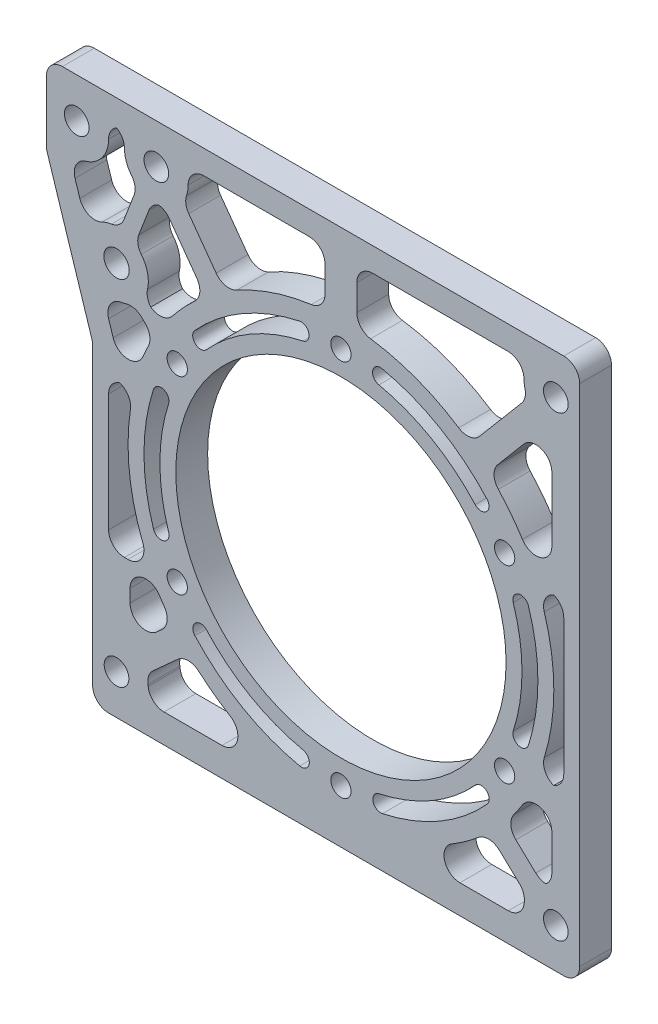
SolidWorks part; units mm, degrees
material "Thornel Mat VMA"
ref_plane "前视基准面" through (0, 0, 0) normal (0, 0, 1) x (1, 0, 0)
ref_plane "上视基准面" through (0, 0, 0) normal (0, 1, 0) x (1, 0, 0)
ref_plane "右视基准面" through (0, 0, 0) normal (1, 0, 0) x (0, 0, -1)
sketch "草图1" plane through (0, 0, 0) normal (0, 0, 1) x (1, 0, 0)
  line L0 (0, 27) -> (27, 27) construction
  line L1 (27, 27) -> (27, 0) construction
  line L2 (0, 27) -> (-37, 27) construction
  line L3 (-37, 27) -> (-31.2, 8.8931)
  line L4 (0, 0) -> (0, 50000) construction
  line L5 (-37, 27) -> (-37, 37)
  line L6 (-37, 37) -> (27, 37)
  line L7 (27, 37) -> (27, 27) construction
  line L8 (27, 37) -> (30, 37)
  line L9 (30, 37) -> (30, -30.45)
  line L10 (0, -27) -> (27, -27) construction
  line L11 (-31.2, -30.45) -> (-31.2, 8.8931)
  line L12 (-31.2, -30.45) -> (30, -30.45)
  circle A0 centre (0, 0) radius 18.5 construction
  circle A1 centre (0, 0) radius 20.75
  circle A2 centre (-28.2, 19) radius 1.6
  circle A3 centre (0, 0) radius 27
  circle A4 centre (0, 0) radius 23.75 construction
  circle A5 centre (0, 23.75) radius 1.275
  circle A6 centre (20.5681, 11.875) radius 1.275
  circle A7 centre (20.5681, -11.875) radius 1.275
  circle A8 centre (0, -23.75) radius 1.275
  circle A9 centre (-20.5681, -11.875) radius 1.275
  circle A10 centre (-20.5681, 11.875) radius 1.275
  circle A11 centre (-33.2, 32) radius 1.55
  circle A12 centre (-23.2, 32) radius 1.55
  circle A13 centre (27, 32) radius 1.55
  circle A14 centre (27, -25.45) radius 1.55
  circle A15 centre (-28.2, -25.45) radius 1.55
  point P12 (0, 0)
  point P30 (0, 0)
  dimension "D2" = 3
  dimension "D5" = 3.2
  dimension "D6" = 54
  dimension "D7" = 47.5
  dimension "D8" = 2.55
  dimension "D12" = 37
  dimension "D14" = 3.1
  dimension "D3" = 19
  dimension "D4" = 28.2
  dimension "D10" = 10
  dimension "D11" = 37
  dimension "D13" = 10
  dimension "D15" = 5
  dimension "D16" = 5
  dimension "D17" = 5
  dimension "D18" = 5
  dimension "D19" = 3
  dimension "D20" = 3
  dimension "D21" = 3
  dimension "D9" = 6
extrude "凸台-拉伸1" add sketch "草图1" along normal blind 4 contours A3 L2 L3 | A3 A1 A2 | A3 L1 L0 region at (-36.0493, 32, 0) region at (-26.2363, 0, 0)
sketch "草图3" plane through (0, 0, 4) normal (0, 0, 1) x (1, 0, 0)
  line L0 (-19.7359, 34) -> (23.5359, 34)
  line L1 (-19.7359, 34) -> (-37, 34)
  line L2 (-37, 27) -> (-37, 37) construction
  line L3 (-37, 37) -> (30, 37) construction
  line L4 (-34.2118, 28.1301) -> (-31.8273, 20.686)
  line L5 (-37, 27) -> (-31.2, 8.8931) construction
  line L6 (-22.1882, 28.1301) -> (-24.5727, 20.686)
  line L7 (-28.2, 19) -> (-28.2, 50019) construction
  line L8 (-30.1727, 15.5203) -> (-26.6293, 4.4585)
  line L9 (26.5, -21.4814) -> (26.5, 28.0314)
  line L10 (30, 37) -> (30, -30.45) construction
  line L11 (-26.5, -5.172) -> (-26.5, -21.8292)
  line L13 (-24.453, -26.85) -> (23.253, -26.85)
  line L15 (-31.2, -30.45) -> (30, -30.45) construction
  line L16 (-31.2, -30.45) -> (-31.2, 8.8931) construction
  circle A0 centre (-33.2, 32) radius 4
  circle A1 centre (-23.2, 32) radius 4
  circle A2 centre (-28.2, 19) radius 4
  circle A3 centre (0, 0) radius 27
  circle A4 centre (27, 32) radius 4
  circle A5 centre (27, -25.45) radius 4
  circle A6 centre (-28.2, -25.45) radius 4
  dimension "D1" = 8
  dimension "D2" = 54
  dimension "D3" = 3
  dimension "D4" = 3
  dimension "D5" = 3.5
  dimension "D6" = 4.7
  dimension "D7" = 3.6
extrude "切除-拉伸1" cut sketch "草图3" against normal blind 10 contours A6 L13 A3 L11 | A5 L9 A3 L13 | L7 L8 A3 L9 A4 L0 A1 L6 A2 | L7 A2 L6 A1 L1 | A2 L7 L1 A0 L4 | L8 L7 A2 region at (1.9, 33.3609, 4) region at (-25.9532, 26.545, 4) region at (-30.4468, 26.545, 4) region at (20.1386, -20.8992, 4) region at (-20.3304, -21.0579, 4)
sketch "草图4" plane through (0, 0, 4) normal (0, 0, 1) x (1, 0, 0)
  line L0 (27, 32) -> (0, 0) construction
  line L1 (0, 23.75) -> (0, 34) construction
  line L2 (-19.7359, 34) -> (23.5359, 34) construction
  line L3 (-23.2, 32) -> (-28.2, 19) construction
  line L4 (-28.2, 19) -> (-20.5681, 11.875) construction
  line L5 (-23.2, 32) -> (0, 0) construction
  line L6 (-28.2, -25.45) -> (0, 0) construction
  line L7 (0, 0) -> (27, -25.45) construction
  line L8 (-26.5163, 16.06) -> (-22.8718, 12.6577)
  line L9 (-22.8718, 12.6577) -> (-21.507, 14.1196)
  line L10 (-21.507, 14.1196) -> (-25.814, 18.1406)
  line L11 (-25.814, 18.1406) -> (-26.5163, 16.06)
  line L12 (-25.0737, 29.9142) -> (-28.3491, 21.3981)
  line L13 (-28.3491, 21.3981) -> (-26.2063, 21.3981)
  line L14 (-26.2063, 21.3981) -> (-23.207, 29.1962)
  line L15 (-23.207, 29.1962) -> (-25.0737, 29.9142)
  line L16 (-22.69, 28.741) -> (-16.3916, 20.0536)
  line L17 (-16.3916, 20.0536) -> (-13.9627, 21.8145)
  line L18 (-13.9627, 21.8145) -> (-20.4351, 30.7419)
  line L19 (-20.4351, 30.7419) -> (-22.69, 28.741)
  line L20 (-2, 25.0688) -> (-2, 35.2606)
  line L21 (-2, 35.2606) -> (2, 34.6837)
  line L22 (2, 34.6837) -> (2, 26.1585)
  line L23 (2, 26.1585) -> (-2, 25.0688)
  line L24 (15.1447, 20.2753) -> (23.8122, 30.548)
  line L25 (23.8122, 30.548) -> (26.1051, 28.6133)
  line L26 (26.1051, 28.6133) -> (17.5116, 18.4284)
  line L27 (17.5116, 18.4284) -> (15.1447, 20.2753)
  line L28 (-20.4084, -16.1282) -> (-27.3665, -22.4078)
  line L29 (-27.3665, -22.4078) -> (-25.3565, -24.6349)
  line L30 (-25.3565, -24.6349) -> (-17.9616, -17.9612)
  line L31 (-17.9616, -17.9612) -> (-20.4084, -16.1282)
  line L32 (17.1983, -18.2723) -> (23.653, -24.3565)
  line L33 (23.653, -24.3565) -> (25.9418, -22.3912)
  line L34 (25.9418, -22.3912) -> (19.4365, -16.2594)
  line L35 (19.4365, -16.2594) -> (17.1983, -18.2723)
  point P45 (-27.2325, -22.5563)
  dimension "D1" = 1
  dimension "D2" = 1
  dimension "D3" = 1
  dimension "D4" = 1
  dimension "D5" = 1.5
  dimension "D6" = 1.5
  dimension "D7" = 2
  dimension "D8" = 2
  dimension "D9" = 1.5
  dimension "D10" = 1.5
  dimension "D11" = 1.7
  dimension "D12" = 1.3
  dimension "D13" = 1.5
  dimension "D14" = 1.5
extrude "凸台-拉伸2" add sketch "草图4" against normal up to surface (4 mm away) up to face at (20.3414, -20.8658, 0)
fillet "圆角1" radius 2 44 edges at (26.5, 5.172, 2) (26.5, 28.0314, 2) (18.5311, 19.6367, 2) (-26.6641, 34, 2) (-29.7359, 34, 2) (-34.2118, 28.1301, 2) (-31.8273, 20.686, 2) (-27.743, 22.9738, 2) (-25.5237, 28.7441, 2) (-26.6293, 4.4585, 2) (-30.1727, 15.5203, 2) (-26.0514, 15.6261, 2) (-23.5187, 13.2616, 2) (-22.45, 14.9999, 2) (-24.6866, 17.088, 2) (-25.8763, 22.2559, 2) (-23.657, 28.0262, 2) (-22.2379, 28.1174, 2) (-17.0381, 20.9453, 2) (-26.5, -5.172, 2) (-21.1434, -16.7916, 2) (-2.8421, -26.85, 2) (-24.453, -26.85, 2) (-24.5207, -23.8806, 2) (-19.15, -19.0336, 2) (2.8421, -26.85, 2) (23.253, -26.85, 2) (23.2728, -23.9981, 2) (18.5883, -19.5825, 2) (26.5, -5.172, 2) (26.5, -21.4814, 2) (25.3305, -21.815, 2) (20.646, -17.3995, 2) (16.2382, 21.5713, 2) (2, 26.9258, 2) (2, 34, 2) (23.4623, 30.1332, 2) (23.5359, 34, 2) (-19.7359, 34, 2) (-19.8091, 29.8783, 2) (-14.6092, 22.7062, 2) (-2, 26.9258, 2) (-2, 34, 2) (-26.5, -21.6258, 2)
fillet "圆角2" radius 2 1 edges at (25.7552, 28.1986, 2)
sketch "草图5" plane through (0, 0, 4) normal (0, 0, 1) x (1, 0, 0)
  arc A0 (-4.0182, 23.4076) -> (-18.2806, 15.1618) centre (0, 0) ccw construction
  arc A1 (-4.7895, 22.2401) -> (-16.884, 15.2477) centre (0, 0) ccw
  arc A2 (-5.2105, 24.1953) -> (-18.3683, 16.5881) centre (0, 0) ccw
  arc A3 (-18.3683, 16.5881) -> (-16.884, 15.2477) centre (-17.6262, 15.9179) ccw
  arc A4 (-4.7895, 22.2401) -> (-5.2105, 24.1953) centre (-5, 23.2177) ccw
  circle A5 centre (-20.5681, 11.875) radius 1.275 construction
  circle A6 centre (0, 23.75) radius 1.275 construction
  arc A7 (16.8658, 15.2679) -> (4.7629, 22.2458) centre (0, 0) ccw
  arc A8 (18.3485, 16.6101) -> (5.1816, 24.2015) centre (0, 0) ccw
  arc A9 (16.8658, 15.2679) -> (18.3485, 16.6101) centre (17.6071, 15.939) ccw
  arc A10 (5.1816, 24.2015) -> (4.7629, 22.2458) centre (4.9722, 23.2237) ccw
  arc A11 (21.6553, -6.9723) -> (21.6469, 6.9982) centre (0, 0) ccw
  arc A12 (23.559, -7.5852) -> (23.5499, 7.6134) centre (0, 0) ccw
  arc A13 (21.6553, -6.9723) -> (23.559, -7.5852) centre (22.6071, -7.2787) ccw
  arc A14 (23.5499, 7.6134) -> (21.6469, 6.9982) centre (22.5984, 7.3058) ccw
  arc A15 (4.7895, -22.2401) -> (16.884, -15.2477) centre (0, 0) ccw
  arc A16 (5.2105, -24.1953) -> (18.3683, -16.5881) centre (0, 0) ccw
  arc A17 (4.7895, -22.2401) -> (5.2105, -24.1953) centre (5, -23.2177) ccw
  arc A18 (18.3683, -16.5881) -> (16.884, -15.2477) centre (17.6262, -15.9179) ccw
  arc A19 (-16.8658, -15.2679) -> (-4.7629, -22.2458) centre (0, 0) ccw
  arc A20 (-18.3485, -16.6101) -> (-5.1816, -24.2015) centre (0, 0) ccw
  arc A21 (-16.8658, -15.2679) -> (-18.3485, -16.6101) centre (-17.6071, -15.939) ccw
  arc A22 (-5.1816, -24.2015) -> (-4.7629, -22.2458) centre (-4.9722, -23.2237) ccw
  arc A23 (-21.6553, 6.9723) -> (-21.6469, -6.9982) centre (0, 0) ccw
  arc A24 (-23.559, 7.5852) -> (-23.5499, -7.6134) centre (0, 0) ccw
  arc A25 (-21.6553, 6.9723) -> (-23.559, 7.5852) centre (-22.6071, 7.2787) ccw
  arc A26 (-23.5499, -7.6134) -> (-21.6469, -6.9982) centre (-22.5984, -7.3058) ccw
  point P47 (0, 0)
  point P53 (0, 0)
  dimension "D1" = 1
  dimension "D2" = 1
  dimension "D4" = 5
  dimension "D3" = 5
  dimension "D5" = 6
extrude "切除-拉伸2" cut sketch "草图5" against normal blind 10
fillet "圆角3" radius 2 6 edges at (-31.2, 8.8931, 2) (-37, 27, 2) (30, 37, 2) (30, -30.45, 2) (-31.2, -30.45, 2) (-37, 37, 2)
sketch "草图7" plane through (0, 0, 4) normal (0, 0, 1) x (1, 0, 0)
  line L0 (-26.0017, 6.2827) -> (-29.2, 6.2827)
  line L1 (-29.2, 6.2827) -> (-29.2, -12.5161)
  line L2 (-29.2, -12.5161) -> (-23.6413, -12.5161)
  line L3 (-31.2, -28.45) -> (-31.2, 8.5806) construction
  line L4 (28, 10.5161) -> (28, -10.5161)
  line L5 (28, -10.5161) -> (24.5962, -10.5161)
  line L6 (28, 10.5161) -> (24.5962, 10.5161)
  line L7 (30, 35) -> (30, -28.45) construction
  circle A0 centre (0, 0) radius 26.75
  arc A1 (-23.559, 7.5852) -> (-23.5499, -7.6134) centre (0, 0) ccw construction
  arc A2 (-28.6198, 10.6726) -> (-24.8728, 10.5046) centre (-26.7152, 11.2827) ccw construction
  arc A3 (-22.8103, -14.446) -> (-26.5, -15.5161) centre (-24.5, -15.5161) ccw construction
  arc A4 (22.8103, 14.446) -> (26.5, 15.5161) centre (24.5, 15.5161) ccw construction
  arc A5 (26.5, -15.5161) -> (22.8103, -14.446) centre (24.5, -15.5161) ccw construction
  point P20 (28.5329, 26.75)
  point P23 (25.1625, 9.0782)
  dimension "D1" = 2
  dimension "D6" = 5
  dimension "D2" = 2
  dimension "D3" = 5
  dimension "D4" = 3
  dimension "D5" = 5
  dimension "D7" = 2
extrude "切除-拉伸3" cut sketch "草图7" against normal blind 10 contours A0 L5 L4 L6 | A0 L0 L1 L2 region at (-27.4867, -4.2385, 4) region at (26.9179, 0, 4)
fillet "圆角4" radius 2 8 edges at (24.5962, 10.5161, 2) (28, 10.5161, 2) (28, -10.5161, 2) (24.5962, -10.5161, 2) (-29.2, -12.5161, 2) (-29.2, 6.2827, 2) (-26.0017, 6.2827, 2) (-23.6413, -12.5161, 2)
